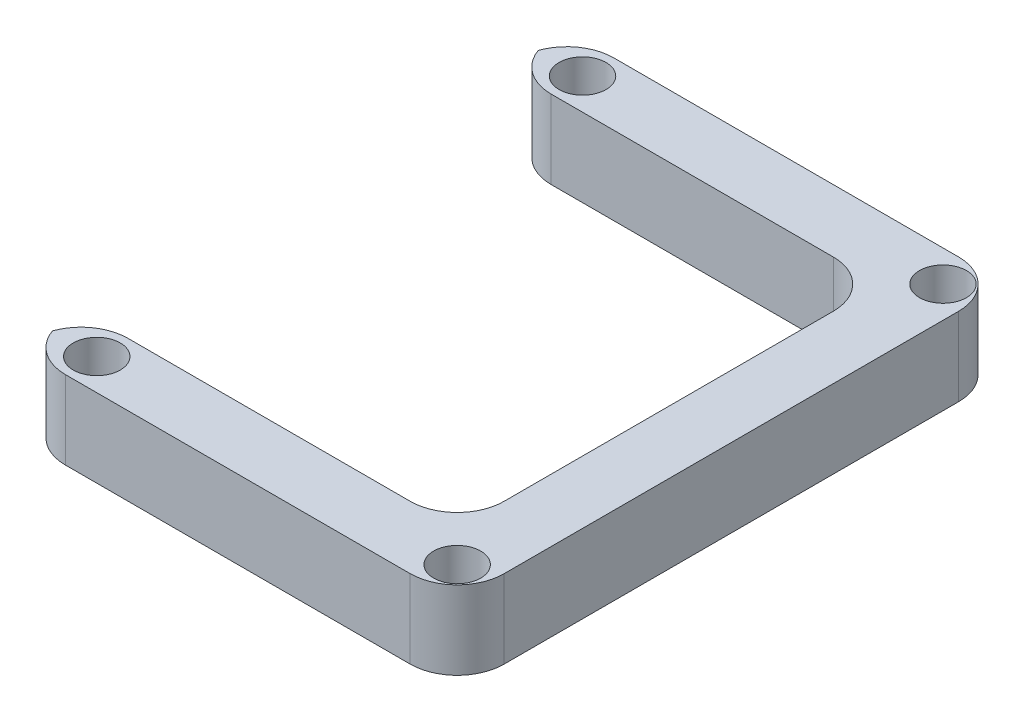
SolidWorks part; units mm, degrees
ref_plane "Front Plane" through (0, 0, 0) normal (0, 0, 1) x (1, 0, 0)
ref_plane "Top Plane" through (0, 0, 0) normal (0, 1, 0) x (1, 0, 0)
ref_plane "Right Plane" through (0, 0, 0) normal (1, 0, 0) x (0, 0, -1)
sketch "Sketch1" plane through (0, 0, 0) normal (0, 1, 0) x (1, 0, 0)
  line L0 (0, 4) -> (24, 4)
  line L1 (0, 0) -> (28, 0)
  line L2 (0, 0) -> (0, 4)
  line L3 (0, 35) -> (28, 35)
  line L4 (28, 0) -> (28, 35)
  line L5 (24, 4) -> (24, 31)
  line L6 (24, 31) -> (0, 31)
  line L7 (0, 0) -> (0, 4)
  line L8 (0, 31) -> (0, 35)
  line L9 (0, 31) -> (0, 35)
  circle A0 centre (3, 2) radius 1.5
  circle A1 centre (3, 33) radius 1.5
  circle A2 centre (26, 33) radius 1.5
  circle A3 centre (26, 2) radius 1.5
  dimension "D6" = 3
  dimension "D7" = 3
  dimension "D8" = 3
  dimension "D9" = 3
  dimension "D1" = 28
  dimension "D2" = 35
  dimension "D3" = 4
  dimension "D4" = 4
  dimension "D5" = 4
  dimension "D10" = 31
  dimension "D11" = 31
  dimension "D12" = 23
  dimension "D13" = 23
  dimension "D14" = 3
  dimension "D15" = 2
  dimension "D16" = 2
  dimension "D17" = 3
extrude "Boss-Extrude1" add sketch "Sketch1" along normal blind 5 contours L8 L6 L5 L0 L2 L1 L4 L3 A3 A2 A1 A0 region at (12, 0, -3.5518)
fillet "Fillet2" radius 3 8 edges at (28, 2.5, -35) (0, 2.5, -35) (0, 2.5, -31) (24, 2.5, -31) (24, 2.5, -4) (0, 2.5, -4) (0, 2.5, 0) (28, 2.5, 0)
